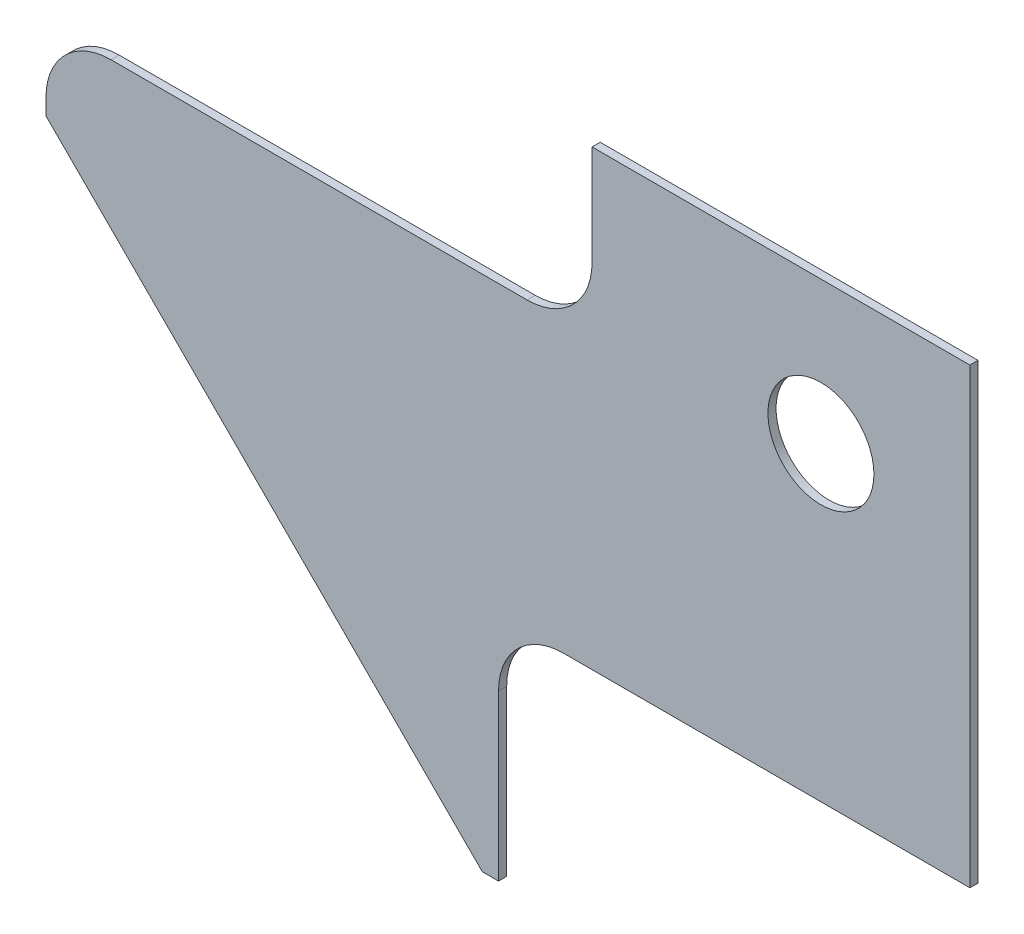
SolidWorks part; units mm, degrees
ref_plane "Front Plane" through (0, 0, 0) normal (0, 0, 1) x (1, 0, 0)
ref_plane "Top Plane" through (0, 0, 0) normal (0, 1, 0) x (1, 0, 0)
ref_plane "Right Plane" through (0, 0, 0) normal (1, 0, 0) x (0, 0, -1)
sketch "Sketch1" plane through (0, 0, 0) normal (0, 0, 1) x (1, 0, 0)
  line L0 (-138.2594, 48.9915) -> (32.2106, -121.4785)
  line L1 (32.2106, -121.4785) -> (222.7106, -121.4785)
  line L2 (-138.2594, 145.2215) -> (-138.2594, 48.9915)
  line L3 (-138.2594, 145.2215) -> (222.7106, 145.2215)
  line L4 (222.7106, -121.4785) -> (222.7106, 145.2215)
  circle A0 centre (164.5153, 89.532) radius 20.701
  circle A2 centre (164.5153, 89.532) radius 64.9605 construction
  circle A3 centre (164.5153, 89.532) radius 302.7747 construction
  point P0 (0, 0)
  point P2 (164.5153, 89.532)
  dimension "D4" = 211.0105
  dimension "D1" = 45
  dimension "D2" = 266.7
  dimension "D5" = 242.7605
extrude "Boss-Extrude1" add sketch "Sketch1" along normal blind 3.175
sketch "Sketch2" plane through (0, 0, 3.175) normal (0, 0, 1) x (1, 0, 0)
  line L0 (32.2106, -121.4785) -> (222.7106, -121.4785) construction
  line L1 (222.7634, -121.4785) -> (38.5606, -121.4785)
  line L2 (222.7634, -121.4785) -> (222.7634, -31.6707)
  line L3 (222.7634, -31.6707) -> (38.5606, -31.6707)
  line L4 (38.5606, -121.4785) -> (38.5606, -31.6707)
extrude "Cut-Extrude1" cut sketch "Sketch2" against normal through all contours L3 L4 L1 L2
fillet "Fillet1" radius 25.4 1 edges at (38.5606, -31.6707, 1.5875)
sketch "Sketch4" plane through (0, 0, 3.175) normal (0, 0, 1) x (1, 0, 0)
  line L1 (-138.2594, 145.2215) -> (-138.2594, 48.9915) construction
  line L3 (-138.2594, 145.2215) -> (75.1006, 145.2215)
  line L4 (-138.2594, 145.2215) -> (-138.2594, 80.7415)
  line L5 (-138.2594, 80.7415) -> (75.1006, 80.7415)
  line L6 (75.1006, 145.2215) -> (75.1006, 80.7415)
extrude "Cut-Extrude2" cut sketch "Sketch4" against normal through all contours L5 L6 L3 L4
fillet "Fillet2" radius 25.4 2 edges at (-138.2594, 80.7415, 1.5875) (75.1006, 80.7415, 1.5875)
